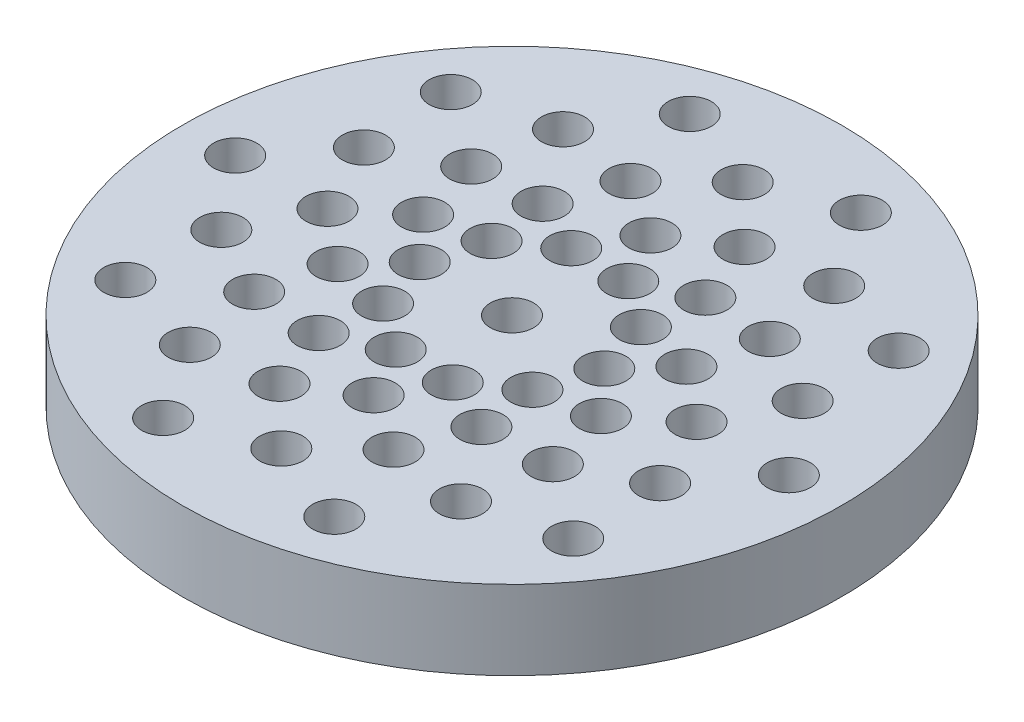
SolidWorks part; units mm, degrees
material "1023 Carbon Steel Sheet (SS)"
ref_plane "Front Plane" through (0, 0, 0) normal (0, 0, 1) x (1, 0, 0)
ref_plane "Top Plane" through (0, 0, 0) normal (0, 1, 0) x (1, 0, 0)
ref_plane "Right Plane" through (0, 0, 0) normal (1, 0, 0) x (0, 0, -1)
sketch "Sketch1" plane through (0, 0, 0) normal (0, 1, 0) x (1, 0, 0)
  circle A0 centre (0, 0) radius 25
  dimension "D1" = 50
extrude "Boss-Extrude1" add sketch "Sketch1" along normal blind 6
sketch "Sketch2" plane through (0, 0, 0) normal (0, -1, 0) x (-1, 0, 0)
  circle A0 centre (0, 0) radius 1.6375
  circle A1 centre (0, 0) radius 1.5875 construction
  point P2 (0, 0)
  dimension "D1" = 0.05
extrude "Cut-Extrude1" cut sketch "Sketch2" against normal through all
pattern_linear "LPattern1" count 4 spacing 7 along (1, 0, 0) of "Cut-Extrude1"
sketch "Sketch3" plane through (0, 0, 0) normal (0, -1, 0) x (1, 0, 0)
  circle A0 centre (0, -10.5) radius 1.6375
  circle A1 centre (0, -10.5) radius 1.5875 construction
  point P2 (0, 0)
  dimension "D1" = 0.05
extrude "Cut-Extrude2" cut sketch "Sketch3" against normal through all
ref_axis "Axis1" through (0, 6.3, 0) along (0, -1, 0)
pattern_linear "LPattern2" count 2 spacing 7 along (0, 0, -1) of "Cut-Extrude2"
pattern_circular "CirPattern1" count 10 over 360 about axis through (0, 6.3, 0) along (0, -1, 0) of "LPattern1", "LPattern2"
